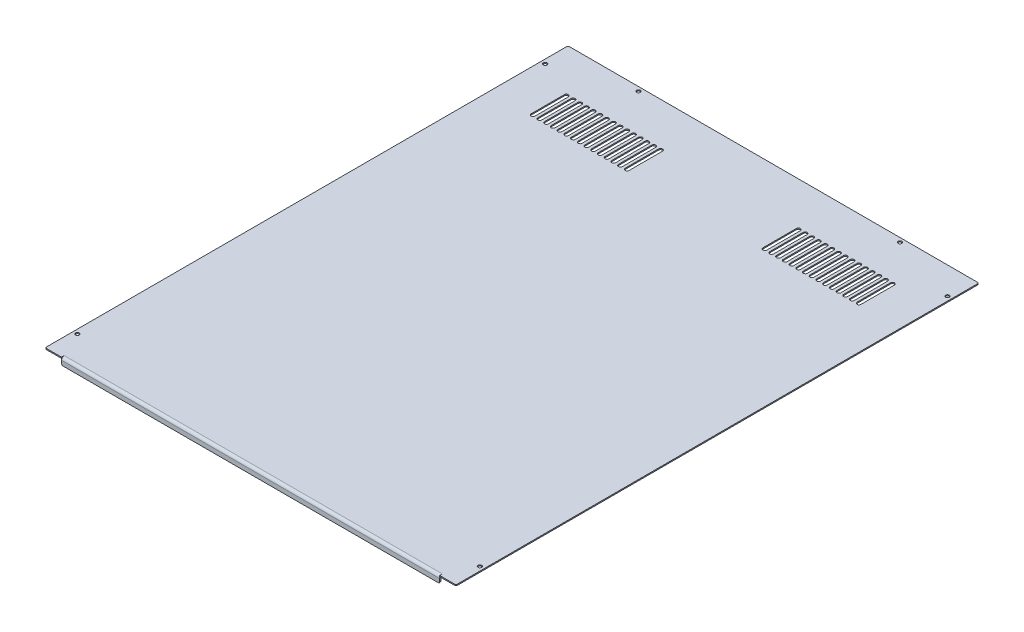
SolidWorks part; units mm, degrees
note: The reader was unsure of these and kept them because the rebuilt part matched: flange length of "Edge-Flange1".
ref_plane "Front" through (0, 0, 0) normal (0, 0, 1) x (1, 0, 0)
ref_plane "Top" through (0, 0, 0) normal (0, 1, 0) x (1, 0, 0)
ref_plane "Right" through (0, 0, 0) normal (1, 0, 0) x (0, 0, -1)
sketch "Sketch1" plane through (0, 0, 0) normal (0, 1, 0) x (1, 0, 0)
  line L0 (0, 0) -> (0, -42.5475) construction
  line L1 (0, 0) -> (220, 0)
  line L2 (0, 0) -> (0, 560)
  line L3 (0, 560) -> (220, 560)
  line L4 (220, 0) -> (220, 560)
  dimension "D1" = 440
  dimension "Length" = 560
sheet metal parameters "Sheet-Metal1" thickness 1.2 parameters "D1"=1.7
base flange "Base-Flange1" sketch "Sketch1" thickness 1.2 reverse thickness direction yes parameters "D1"=1.7
edge flange "Edge-Flange1" sketch "Sketch5" flange angle 90 flange length 6.3 flange position material inside bend radius 1.7 thickness 1.2 relief none parameters "D1"=1.8, "D6"=10
sketch "Sketch5" plane through (0, 0, 0) normal (0, 0, -1) x (1, 0, 0)
  line L1 (220, 0) -> (0, 0) construction
  line L2 (0, 0) -> (0, 6.3)
  line L3 (0, 6.3) -> (202.5, 6.3)
  line L4 (202.5, 6.3) -> (202.5, 0)
  line L5 (202.5, 0) -> (0, 0)
  line L6 (0, 0) -> (0, 88.2532) construction
  line L7 (0, -1.2) -> (220, -1.2) construction
  dimension "D1" = 405
  dimension "D2" = 7.5
bend "EdgeBend1" bend radius 1.7 bend angle 90 parameters "D5"=1
fillet "Fillet1" radius 1.5 1 edges at (202.5, -6.3, -0.6)
sketch "Sketch6" plane through (0, 1.2, 0) normal (0, 1, 0) x (1, 0, 0)
  line L0 (215.5, 30) -> (215.5, 531) construction
  line L1 (202.5, 0) -> (220, 0) construction
  line L2 (0, 0) -> (0, 379.0482) construction
  line L3 (220, 560) -> (0, 560) construction
  circle A0 centre (215.5, 531) radius 2
  circle A1 centre (215.5, 30) radius 2
  circle A2 centre (140, 555.5) radius 2
  dimension "D1" = 4
  dimension "D3" = 30
  dimension "D4" = 431
  dimension "D5" = 280
  dimension "D6" = 525.5
  dimension "D7" = 4.5
  dimension "D8" = 29
  dimension "D2" = 501
extrude "Cut-Extrude1" cut sketch "Sketch6" against normal blind 10
sketch "Sketch7" plane through (0, 1.2, 0) normal (0, 1, 0) x (1, 0, 0)
  line L0 (172.5, 477.1) -> (172.5, 512.9) construction
  line L1 (176.7, 512.9) -> (176.7, 477.1) construction
  line L2 (174.6, 512.9) -> (174.6, 477.1) construction
  line L3 (174.6, 495) -> (220, 495) construction
  line L4 (220, 560) -> (0, 560) construction
  line L5 (220, 0) -> (220, 560) construction
  line L6 (202.5, 0) -> (220, 0) construction
  line L7 (174.6, 477.1) -> (174.6, 512.9) construction
  line L8 (172.5, 477.1) -> (172.5, 512.9)
  line L9 (176.7, 477.1) -> (176.7, 512.9)
  arc A0 (172.5, 512.9) -> (176.7, 512.9) centre (174.6, 512.9) cw construction
  arc A1 (176.7, 477.1) -> (172.5, 477.1) centre (174.6, 477.1) cw construction
  arc A2 (172.5, 477.1) -> (176.7, 477.1) centre (174.6, 477.1) ccw
  arc A3 (176.7, 512.9) -> (172.5, 512.9) centre (174.6, 512.9) ccw
  point P15 (174.6, 495)
  dimension "D2" = 40
  dimension "D1" = 4.2
  dimension "D3" = 495
  dimension "D4" = 45.4
  dimension "D5" = 65
extrude "Cut-Extrude2" cut sketch "Sketch7" against normal blind 10
pattern_linear "LPattern1" count 15 spacing 7.2 along (-1, 0, 0) of "Cut-Extrude2"
fillet "Fillet2" radius 1.5 2 edges at (220, 0.6, -560) (220, 0.6, 0)
mirror "Mirror1" about plane through (0, 1.2, 0) normal (1, 0, 0) of bodies 106 103
flat pattern "Flat-Pattern1" [suppressed]
sketch "Bend-Lines1" plane through (0, 1.2, 0) normal (0, 1, 0) x (-1, 0, 0)
  line L1 (202.5, -1.1501) -> (-202.5, -1.1501) construction
  line L2 (202.5, -1.1501) -> (-202.5, -1.1501) construction
sketch3d "Bounding-Box1" [suppressed]
  line L0 (-220, 0, 0) -> (220, 0, 0) construction
  line L1 (-220, 384.1997, 0) -> (220, 384.1997, 0) construction
  line L2 (-220, 0, 0) -> (-220, 384.1997, 0) construction
  line L3 (220, 0, 0) -> (220, 384.1997, 0) construction
bend of the flat pattern "Flatten-<EdgeBend1>1"
